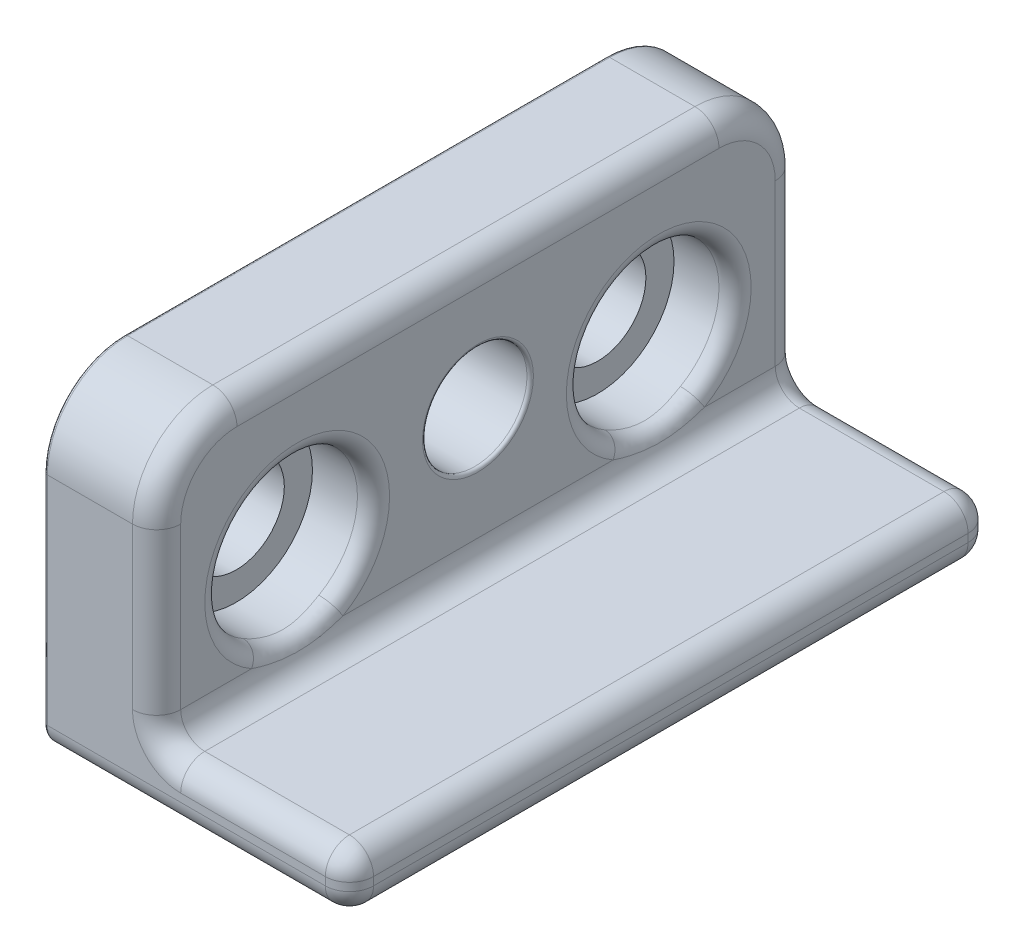
SolidWorks part; units mm, degrees
note: The reader was unsure of these and kept them because the rebuilt part matched: shared geometry of "Sketch1<3>", "Sketch2<3>".
ref_plane "Front Plane" through (0, 0, 0) normal (0, 0, 1) x (1, 0, 0)
ref_plane "Top Plane" through (0, 0, 0) normal (0, 1, 0) x (1, 0, 0)
ref_plane "Right Plane" through (0, 0, 0) normal (1, 0, 0) x (0, 0, -1)
sketch "Sketch1" plane through (0, 0, 0) normal (0, 1, 0) x (1, 0, 0)
  line L1 (8, 2.5) -> (-11, 2.5) construction
  line L2 (8, 2.5) -> (8, -2.5) construction
  line L3 (8, -2.5) -> (-11, -2.5) construction
  line L4 (-11, 2.5) -> (-11, -2.5) construction
  line L5 (-11, 20) -> (-11, -20)
  line L6 (-11, -20) -> (8, -20)
  line L14 (8, -20) -> (8, 20)
  line L15 (8, 20) -> (-11, 20)
  line L16 (-4, 20) -> (-4, -20)
  point P0 (0, 0)
  point P17 (8, 0)
  dimension "D1" = 5
  dimension "D2" = 7
  dimension "D3" = 12
  dimension "D4" = 17.5
  dimension "D5" = 17.5
  dimension "D7" = 4
extrude "Boss-Extrude1" add sketch "Sketch1" along normal mid plane 20 contours L16 L15 L5 L6
extrude "Boss-Extrude2" add sketch "Sketch1<3>" along normal blind 3.5 from surface at -10 contours L15 L16 L6 L14 starting at face at (-7.5, -10, 0)
sketch "Sketch1<3>" plane through (0, 0, 0) normal (0, 1, 0) x (1, 0, 0) same geometry as "Sketch1"
sketch "Sketch2" plane through (-11, 0, 0) normal (-1, 0, 0) x (0, 0, 1)
  line L0 (-20, 10) -> (-20, -10) construction
  line L1 (20, 10) -> (20, -10) construction
  line L3 (-20, 10) -> (20, 10) construction
  circle A0 centre (0, 2) radius 3.25
  circle A1 centre (11.25, 0) radius 3
  circle A2 centre (-11.25, 0) radius 3
  circle A3 centre (-11.25, 0) radius 4.75
  circle A4 centre (11.25, 0) radius 4.75
  point P10 (0, 0)
  point P16 (0, 0)
  dimension "D1" = 6.5
  dimension "D2" = 6
  dimension "D3" = 9.5
  dimension "D4" = 4
  dimension "D5" = 4
  dimension "D6" = 8
extrude "Cut-Extrude1" cut sketch "Sketch2" against normal up to surface (7 mm away) contours A1 | A0 | A2 up to face at (-4, 1.75, 0)
extrude "Cut-Extrude2" cut sketch "Sketch2<3>" along normal offset from surface (3.8 mm away) 3.2 from surface at -7 contours A3 A2 | A4 A1 up to face at (-11, 0, 14.25) starting at face at (-4, 0, 8.25)
sketch "Sketch2<3>" plane through (-11, 0, 0) normal (-1, 0, 0) x (0, 0, 1) same geometry as "Sketch2"
fillet "Fillet5" radius 5 2 edges at (-7.5, 10, 20) (-7.5, 10, -20)
fillet "Fillet6" radius 1.5 14 edges at (-4, -0.75, 20) (2, -6.5, 20) (-4, -6.5, 0) (8, -10, 0) (8, -6.5, 0) (-4, -0.75, -20) (2, -6.5, -20) (-4, 10, 0) (-4, 8.5355, 18.5355) (-4, 8.5355, -18.5355) (-1.5, -10, 20) (-1.5, -10, -20) (8, -8.25, -20) (8, -8.25, 20)
fillet "Fillet7" radius 1 2 edges at (-4, 0, -16) (-4, 0, 6.5)
fillet "Fillet8" radius 0.2 12 edges at (-11, -1.75, 20) (-11, -1.75, -20) (-11, 0, -8.25) (-11, 2, 3.25) (-11, 0, 14.25) (-4, 2, -3.25) (-11, 10, 0) (-11, -10, 0) (-11, 8.5355, -18.5355) (-11, 8.5355, 18.5355) (-11, -9.5607, -19.5607) (-11, -9.5607, 19.5607)
